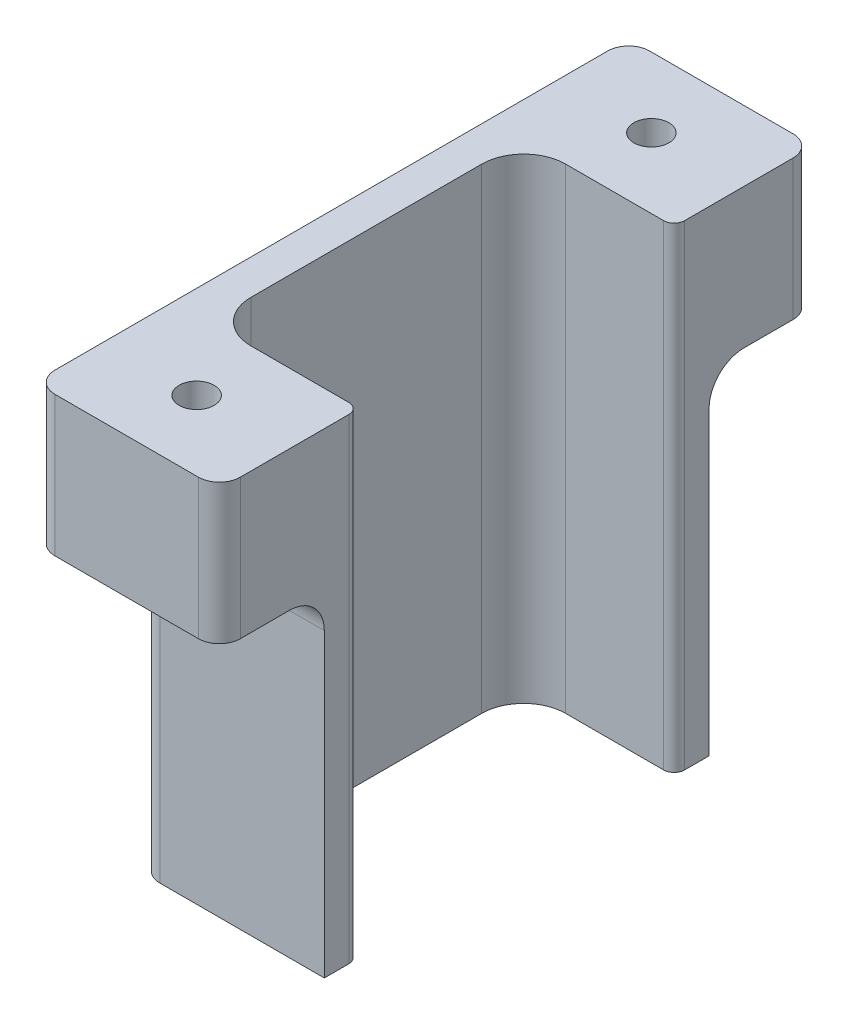
SolidWorks part; units mm, degrees
material "K110"
ref_plane "Front Plane" through (0, 0, 0) normal (0, 0, 1) x (1, 0, 0)
ref_plane "Top Plane" through (0, 0, 0) normal (0, 1, 0) x (1, 0, 0)
ref_plane "Right Plane" through (0, 0, 0) normal (1, 0, 0) x (0, 0, -1)
sketch "Sketch1" plane through (0, 0, 0) normal (0, 1, 0) x (1, 0, 0)
  line L1 (-17.88, 42.5) -> (8.62, 42.5)
  line L2 (-17.88, 42.5) -> (-17.88, -42.5)
  line L3 (-17.88, -42.5) -> (8.62, -42.5)
  line L4 (8.62, 42.5) -> (8.62, -42.5)
  line L5 (8.62, -39.5) -> (8.62, -24) construction
  line L7 (5.62, 42.5) -> (-14.88, 42.5) construction
  line L8 (-14.88, -42.5) -> (5.62, -42.5) construction
  line L10 (-17.88, 39.5) -> (-17.88, -39.5) construction
  point P0 (0, 0)
extrude "Boss-Extrude1" add sketch "Sketch1" against normal blind 68
fillet "Fillet1" radius 3 4 edges at (-17.88, -34, -42.5) (8.62, -34, -42.5) (-17.88, -34, 42.5) (8.62, -34, 42.5)
sketch "Sketch2" plane through (0, 0, 0) normal (0, 1, 0) x (1, 0, 0)
  line L0 (7.12, -22.5) -> (-6.88, -22.5) construction
  line L1 (-12.88, -16.5) -> (-12.88, 16.5) construction
  line L2 (-6.88, 22.5) -> (7.12, 22.5) construction
  line L3 (7.12, -22.5) -> (-6.88, -22.5)
  line L4 (-12.88, -16.5) -> (-12.88, 16.5)
  line L5 (-6.88, 22.5) -> (7.12, 22.5)
  line L6 (8.62, 24) -> (8.62, -24)
  arc A0 (8.62, -24) -> (7.12, -22.5) centre (7.12, -24) ccw construction
  arc A1 (-12.88, -16.5) -> (-6.88, -22.5) centre (-6.88, -16.5) ccw construction
  arc A2 (-6.88, 22.5) -> (-12.88, 16.5) centre (-6.88, 16.5) ccw construction
  arc A3 (7.12, 22.5) -> (8.62, 24) centre (7.12, 24) ccw construction
  arc A4 (8.62, -24) -> (7.12, -22.5) centre (7.12, -24) ccw
  arc A5 (-12.88, -16.5) -> (-6.88, -22.5) centre (-6.88, -16.5) ccw
  arc A6 (-6.88, 22.5) -> (-12.88, 16.5) centre (-6.88, 16.5) ccw
  arc A7 (7.12, 22.5) -> (8.62, 24) centre (7.12, 24) ccw
extrude "Cut-Extrude1" cut sketch "Sketch2" against normal up to next
sketch "Sketch3" plane through (0, -68, 0) normal (0, 1, 0) x (1, 0, 0)
  line L0 (-17.88, 39.5) -> (-17.88, -39.5) construction
  line L1 (8.62, -39.5) -> (8.62, -24) construction
  line L2 (-14.88, -27.5) -> (8.62, -27.5) construction
  line L3 (-17.88, -24.5) -> (-17.88, -39.5)
  line L4 (8.62, -39.5) -> (8.62, -27.5)
  line L5 (-14.88, -27.5) -> (8.62, -27.5)
  line L6 (-14.88, -42.5) -> (5.62, -42.5)
  line L7 (-17.88, 0) -> (-12.88, 0) construction
  line L8 (-17.88, 24.5) -> (-17.88, -24.5) construction
  line L9 (-12.88, 16.5) -> (-12.88, -16.5) construction
  line L10 (-14.88, 42.5) -> (5.62, 42.5)
  line L11 (-14.88, 27.5) -> (8.62, 27.5)
  line L12 (8.62, 39.5) -> (8.62, 27.5)
  line L13 (-17.88, 24.5) -> (-17.88, 39.5)
  arc A0 (5.62, -42.5) -> (8.62, -39.5) centre (5.62, -39.5) ccw construction
  arc A1 (-17.88, -39.5) -> (-14.88, -42.5) centre (-14.88, -39.5) ccw construction
  arc A2 (-17.88, -24.5) -> (-14.88, -27.5) centre (-14.88, -24.5) ccw construction
  arc A3 (5.62, -42.5) -> (8.62, -39.5) centre (5.62, -39.5) ccw
  arc A4 (-17.88, -39.5) -> (-14.88, -42.5) centre (-14.88, -39.5) ccw
  arc A5 (-17.88, -24.5) -> (-14.88, -27.5) centre (-14.88, -24.5) ccw
  arc A6 (-17.88, 24.5) -> (-14.88, 27.5) centre (-14.88, 24.5) cw
  arc A7 (-17.88, 39.5) -> (-14.88, 42.5) centre (-14.88, 39.5) cw
  arc A8 (5.62, 42.5) -> (8.62, 39.5) centre (5.62, 39.5) cw
extrude "Cut-Extrude2" cut sketch "Sketch3" along a picked direction on the side of the normal blind 48 contours L13 A6 L11 L12 A8 L10 A7 | L6 A3 L4 L5 A5 L3 A4
mirror "Mirror1" about plane through (0, 0, 0) normal (0, 0, 1) of "Cut-Extrude2"
fillet "Fillet2" radius 5 4 edges at (-17.0013, -20, -26.6213) (-17.0013, -20, 26.6213) (-3.13, -20, -27.5) (-3.13, -20, 27.5)
hole_wizard "M6 Tapped Hole1" positions "Sketch8" profile "Sketch6" tap size "M6" standard "ISO"
sketch "Sketch8" plane through (0, 0, 0) normal (0, 1, 0) x (1, 0, 0)
  line L0 (-4.63, 42.5) -> (-4.63, 22.5) construction
  line L1 (5.62, 42.5) -> (-14.88, 42.5) construction
  line L2 (7.12, 22.5) -> (-6.88, 22.5) construction
  line L4 (-4.63, -42.5) -> (-4.63, -22.5) construction
  line L5 (-14.88, -42.5) -> (5.62, -42.5) construction
  line L6 (-6.88, -22.5) -> (7.12, -22.5) construction
  point P0 (-4.63, 32.5)
  point P3 (-4.63, -32.5)
sketch "Sketch6" plane through (-4.63, 0, -32.5) normal (1, 0, 0) x (0, 0, 1)
  line L0 (0, 0) -> (0, 16.5022)
  line L1 (0, 16.5022) -> (2.5, 15)
  line L2 (2.5, 15) -> (2.5, 0)
  line L5 (2.5, 0) -> (0, 0)
  line L10 (0, 16.5022) -> (-2.5, 15) construction
  line L11 (0, -6.35) -> (0, 107.95) construction
  dimension "Tap Drill Dia." = 5
  dimension "Tap Drill Depth" = 15
  dimension "Drill Angle" = 118
cosmetic thread "Hole Thread1"
cosmetic thread "Hole Thread2"
